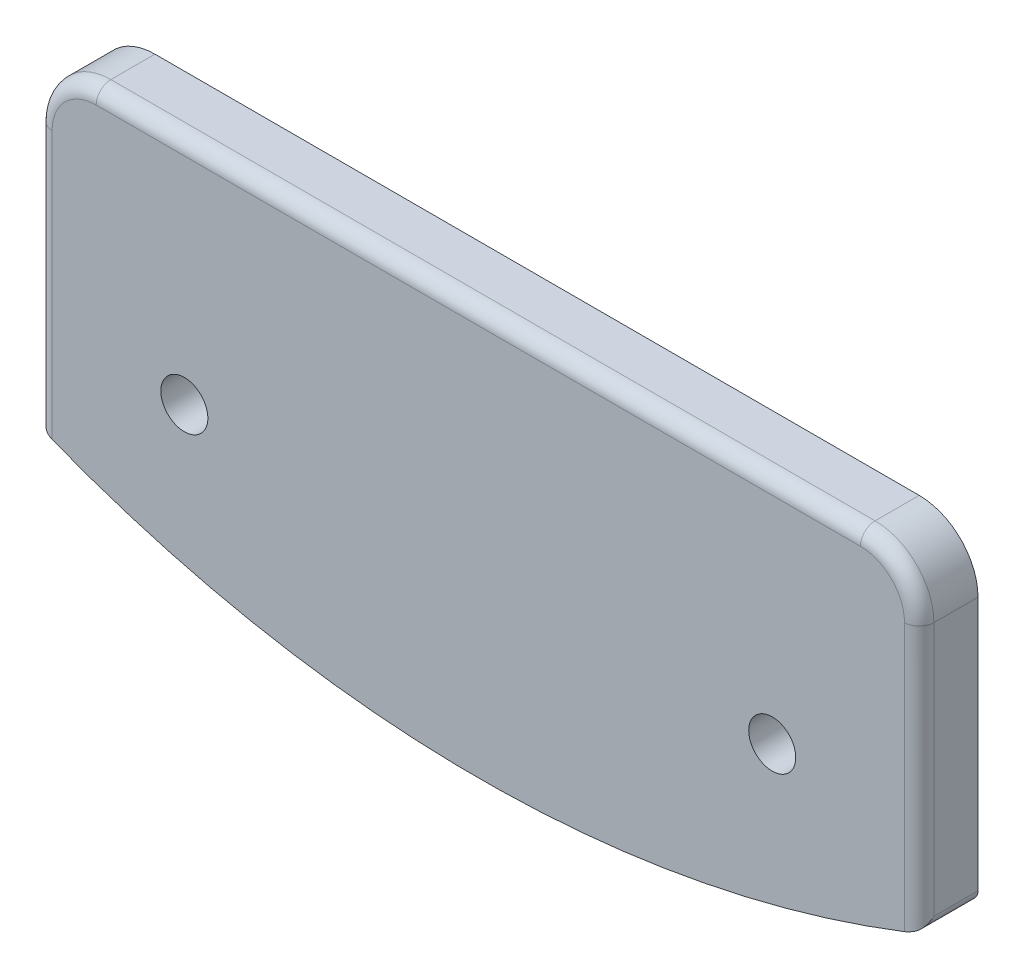
SolidWorks part; units mm, degrees
ref_plane "Спереди" through (0, 0, 0) normal (0, 0, 1) x (1, 0, 0)
ref_plane "Сверху" through (0, 0, 0) normal (0, 1, 0) x (1, 0, 0)
ref_plane "Справа" through (0, 0, 0) normal (1, 0, 0) x (0, 0, -1)
sketch "Эскиз1" plane through (0, 0, 0) normal (0, 0, 1) x (1, 0, 0)
  line L0 (0, -1.246) -> (0, -50001.246) construction
  line L1 (-26, -52.35) -> (26, -52.35)
  line L2 (-26, -53.35) -> (2.65, -53.35)
  line L3 (-29, -56.35) -> (-29, -64)
  line L4 (-29, -64) -> (5.65, -64)
  line L5 (5.65, -56.35) -> (5.65, -64)
  line L7 (-30, -56.35) -> (-30, -74.162)
  line L10 (30, -56.35) -> (30, -74.162)
  arc A1 (-26, -53.35) -> (-29, -56.35) centre (-26, -56.35) ccw
  arc A2 (5.65, -56.35) -> (2.65, -53.35) centre (2.65, -56.35) ccw
  arc A3 (-59.4802, -53.4986) -> (59.4802, -53.4986) centre (0, 0) ccw construction
  arc A4 (-30, -74.162) -> (30, -74.162) centre (0, 0) ccw
  circle A5 centre (-20, -68) radius 1.6
  circle A6 centre (20, -68) radius 1.6
  circle A7 centre (-22.55, -54.35) radius 0.5 construction
  circle A8 centre (4.65, -62.45) radius 0.5 construction
  arc A9 (-30, -56.35) -> (-26, -52.35) centre (-26, -56.35) cw
  arc A11 (30, -56.35) -> (26, -52.35) centre (26, -56.35) ccw
  point P3 (-20, -68)
  point P9 (20, -68)
  dimension "D1" = 3.2
  dimension "D4" = 0.5
  dimension "D6" = 0.5
  dimension "D8" = 3
  dimension "D3" = 0.5
  dimension "D5" = 0.5
  dimension "D7" = 1
extrude "Бобышка-Вытянуть1" add sketch "Эскиз1" along normal blind 2.5
extrude "Бобышка-Вытянуть2" add sketch "Эскиз1<2>" along normal blind 1.5 from surface contours A4 L10 A11 L1 A9 L7 | A5 | A6 starting at face at (18.4, -68, 2.5)
sketch "Эскиз1<2>" plane through (0, 0, 0) normal (0, 0, 1) x (1, 0, 0) same geometry as "Эскиз1"
fillet "Скругление1" radius 1 2 edges at (-29, -64, 1.25) (5.65, -64, 1.25)
fillet "Скругление2" radius 1 5 edges at (-30, -65.256, 4) (-28.8284, -53.5216, 4) (0, -52.35, 4) (28.8284, -53.5216, 4) (30, -65.256, 4)
fillet "Скругление3" radius 0.75 2 edges at (-30, -74.162, 1.5) (30, -74.162, 1.5) tangent propagation no
mirror "Зеркальное отражение1" [suppressed] about plane through (0, 0, 0) normal (1, 0, 0) of bodies 104
delete or keep bodies "Тело-Удалить/Сохранить 1" [suppressed] type delete bodies bodies 104
